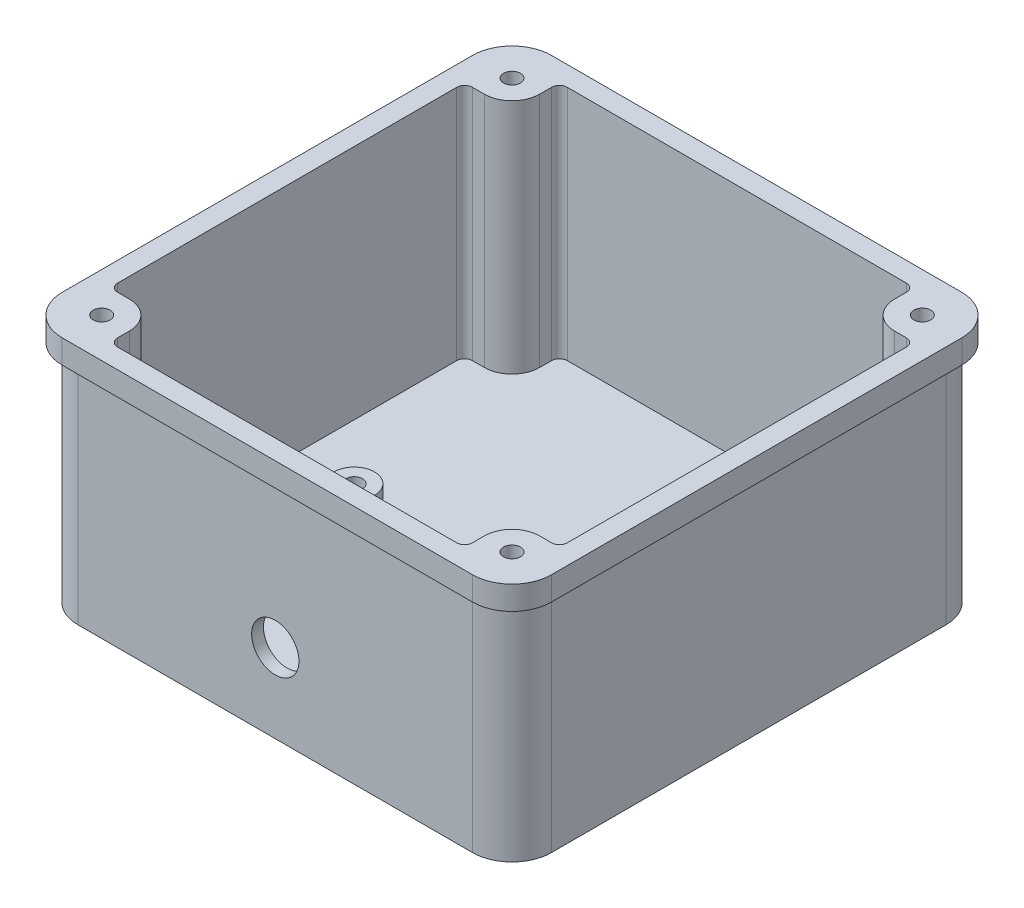
SolidWorks part; units mm, degrees
ref_plane "Front Plane" through (0, 0, 0) normal (0, 0, 1) x (1, 0, 0)
ref_plane "Top Plane" through (0, 0, 0) normal (0, 1, 0) x (1, 0, 0)
ref_plane "Right Plane" through (0, 0, 0) normal (1, 0, 0) x (0, 0, -1)
sketch "Sketch1" plane through (0, 0, 0) normal (0, 1, 0) x (1, 0, 0)
  line L1 (-60, 60) -> (60, 60)
  line L2 (-60, 60) -> (-60, -60)
  line L3 (-60, -60) -> (60, -60)
  line L4 (60, 60) -> (60, -60)
  line L5 (-60, 60) -> (60, -60) construction
  line L6 (-60, -60) -> (60, 60) construction
  point P0 (0, 0)
  dimension "D1" = 120
  dimension "D2" = 120
extrude "Boss-Extrude1" add sketch "Sketch1" along normal blind 63
shell "Shell1" thickness 3 removed face at (0, 63, 0)
sketch "Sketch2" plane through (0, 3, 0) normal (0, 1, 0) x (1, 0, 0)
  line L0 (0, 60) -> (0, -60) construction
  line L1 (60, 60) -> (-60, 60) construction
  line L2 (-60, -60) -> (60, -60) construction
  line L3 (-60, 0) -> (60, 0) construction
  line L4 (-60, 60) -> (-60, -60) construction
  line L5 (60, -60) -> (60, 60) construction
  line L6 (-60, 52) -> (-52, 52) construction
  line L7 (-52, 52) -> (-52, 60) construction
  line L21 (-52, -52) -> (-52, -60) construction
  line L22 (-60, -52) -> (-52, -52) construction
  line L36 (52, 44.98) -> (55, 44.98)
  line L41 (44.98, 52) -> (44.98, 55)
  line L43 (-44.98, 52) -> (-44.98, 55)
  line L44 (-52, 44.98) -> (-55, 44.98)
  line L45 (-57, 42.98) -> (-57, 57)
  line L46 (-57, 57) -> (-42.98, 57)
  line L47 (57, 57) -> (42.98, 57)
  line L48 (57, 42.98) -> (57, 57)
  line L49 (57, -42.98) -> (57, -57)
  line L50 (57, -57) -> (42.98, -57)
  line L51 (44.98, -52) -> (44.98, -55)
  line L52 (52, -44.98) -> (55, -44.98)
  line L53 (-52, -44.98) -> (-55, -44.98)
  line L54 (-44.98, -52) -> (-44.98, -55)
  line L55 (-57, -57) -> (-42.98, -57)
  line L56 (-57, -42.98) -> (-57, -57)
  circle A0 centre (-52, 52) radius 2.15
  arc A1 (-52, 44.98) -> (-44.98, 52) centre (-52, 52) ccw
  circle A2 centre (-52, 52) radius 7.02 construction
  circle A5 centre (52, 52) radius 2.15
  circle A12 centre (52, -52) radius 2.15
  circle A16 centre (-52, -52) radius 2.15
  arc A19 (-57, 42.98) -> (-55, 44.98) centre (-55, 42.98) cw
  arc A20 (-42.98, 57) -> (-44.98, 55) centre (-42.98, 55) ccw
  arc A21 (57, 42.98) -> (55, 44.98) centre (55, 42.98) ccw
  arc A22 (52, 44.98) -> (44.98, 52) centre (52, 52) cw
  arc A23 (42.98, 57) -> (44.98, 55) centre (42.98, 55) cw
  arc A24 (42.98, -57) -> (44.98, -55) centre (42.98, -55) ccw
  arc A25 (52, -44.98) -> (44.98, -52) centre (52, -52) ccw
  arc A26 (57, -42.98) -> (55, -44.98) centre (55, -42.98) cw
  arc A27 (-57, -42.98) -> (-55, -44.98) centre (-55, -42.98) ccw
  arc A28 (-52, -44.98) -> (-44.98, -52) centre (-52, -52) cw
  arc A29 (-42.98, -57) -> (-44.98, -55) centre (-42.98, -55) cw
  dimension "D1" = 8
  dimension "D4" = 4.3
  dimension "D3" = 2
  dimension "D2" = 8
extrude "Boss-Extrude2" add sketch "Sketch2" along normal blind 60
sketch "Sketch3" plane through (0, 63, 0) normal (0, 1, 0) x (1, 0, 0)
  line L0 (-60, -60) -> (60, -60) construction
  line L1 (60, -60) -> (60, 60) construction
  line L2 (-60, 60) -> (-60, -60) construction
  line L3 (60, 60) -> (-60, 60) construction
  line L4 (-60, -60) -> (60, -60)
  line L5 (60, -60) -> (60, 60)
  line L6 (-60, 60) -> (-60, -60)
  line L7 (60, 60) -> (-60, 60)
  line L8 (62, 62) -> (-62, 62)
  line L9 (-62, 62) -> (-62, -62)
  line L10 (-62, -62) -> (62, -62)
  line L11 (62, -62) -> (62, 62)
  dimension "D1" = 2
extrude "Boss-Extrude3" add sketch "Sketch3" against normal blind 6
fillet "Fillet1" radius 10 8 edges at (62, 60, 62) (60, 28.5, 60) (62, 60, -62) (60, 28.5, -60) (-62, 60, -62) (-60, 28.5, -60) (-62, 60, 62) (-60, 28.5, 60)
sketch "Sketch4" plane through (0, 3, 0) normal (0, 1, 0) x (1, 0, 0)
  line L0 (-62, 0) -> (62, 0) construction
  line L1 (-62, 52) -> (-62, -52) construction
  line L2 (62, -52) -> (62, 52) construction
  line L4 (52, 62) -> (-52, 62) construction
  line L5 (0, 62) -> (0, -62) construction
  line L6 (-52, -62) -> (52, -62) construction
  circle A0 centre (-40, 0) radius 2.15
  circle A1 centre (40, 0) radius 2.15
  dimension "D1" = 4.3
  dimension "D2" = 80
extrude "Cut-Extrude1" cut sketch "Sketch4" against normal blind 3
sketch "Sketch5" plane through (0, 3, 0) normal (0, 1, 0) x (1, 0, 0)
  line L0 (0, 62) -> (0, -62) construction
  line L1 (52, 62) -> (-52, 62) construction
  line L2 (-52, -62) -> (52, -62) construction
  circle A0 centre (-40, 0) radius 2.15 construction
  circle A1 centre (-40, 0) radius 2.15
  circle A2 centre (-40, 0) radius 5.15
  circle A3 centre (40, 0) radius 2.15
  circle A4 centre (40, 0) radius 5.15
  dimension "D1" = 3
extrude "Boss-Extrude4" add sketch "Sketch5" along normal blind 3
sketch "Sketch6" plane through (0, 0, 60) normal (0, 0, 1) x (1, 0, 0)
  line L0 (0, 20) -> (0, 0) construction
  circle A0 centre (0, 20) radius 6
  dimension "D1" = 12
  dimension "D2" = 20
extrude "Cut-Extrude2" cut sketch "Sketch6" against normal blind 10
ref_plane "Plane1" through (0, 0, 35) normal (0, 0, 1) x (1, 0, 0)
sketch "Sketch7" plane through (0, 0, 35) normal (0, 0, 1) x (1, 0, 0)
  point P0 (0, 20)
other "CPoint1" parameters "Diameter"=3, "StubLength"=4
ref_axis "Axis1" through (0, 20, 45) along (0, 0, -1)
